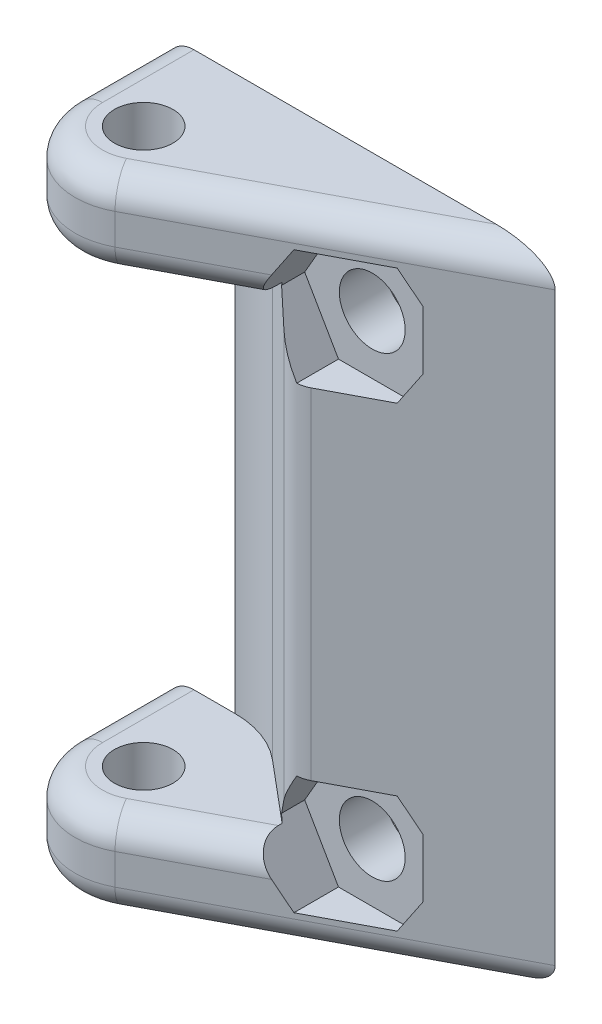
SolidWorks part; units mm, degrees
ref_plane "Front Plane" through (0, 0, 0) normal (0, 0, 1) x (1, 0, 0)
ref_plane "Top Plane" through (0, 0, 0) normal (0, 1, 0) x (1, 0, 0)
ref_plane "Right Plane" through (0, 0, 0) normal (1, 0, 0) x (0, 0, -1)
sketch "Sketch1" plane through (0, 0, 0) normal (0, 1, 0) x (1, 0, 0)
  line L2 (-4.7625, 6.35) -> (-4.7625, 0)
  line L3 (2.2238, -4.2114) -> (22.225, 6.35)
  line L4 (22.225, 6.35) -> (-4.7625, 6.35)
  circle A0 centre (0, 0) radius 2.032
  arc A1 (-4.7625, 0) -> (2.2238, -4.2114) centre (0, 0) ccw
  dimension "D1" = 4.064
  dimension "D2" = 22.225
  dimension "D4" = 4.7625
  dimension "D5" = 6.35
extrude "Boss-Extrude1" add sketch "Sketch1" along normal mid plane 44.45
sketch "Sketch6" plane through (0, 0, 0) normal (0, 1, 0) x (1, 0, 0)
  line L0 (0, 6.35) -> (-4.7625, 6.35)
  line L1 (-4.7625, 6.35) -> (-4.7625, 0) construction
  line L2 (-4.7625, 6.35) -> (-4.7625, 0)
  line L3 (4.0817, 4.8644) -> (10.0027, -0.1039)
  line L4 (2.2238, -4.2114) -> (22.225, 6.35) construction
  line L5 (10.0027, -0.1039) -> (2.2238, -4.2114)
  arc A0 (-4.7625, 0) -> (2.2238, -4.2114) centre (0, 0) ccw
  arc A2 (4.0817, 4.8644) -> (0, 6.35) centre (0, 0) ccw
  dimension "D1" = 6.35
  dimension "D2" = 140
extrude "Cut-Extrude4" cut sketch "Sketch6" against normal mid plane 32.5437
sketch "Sketch13" plane through (0, 0, -6.35) normal (0, 0, -1) x (-1, 0, 0)
  line L0 (-12.7, 15.875) -> (-12.7, -15.875) construction
  circle A0 centre (-12.7, 15.875) radius 2.286
  circle A1 centre (-12.7, -15.875) radius 2.286
  point P4 (-12.7, 0)
  dimension "D1" = 4.572
  dimension "D2" = 31.75
  dimension "D3" = 12.7
extrude "Cut-Extrude9" cut sketch "Sketch13" against normal through all
sketch "Sketch14" plane through (0, 0, -6.35) normal (0, 0, -1) x (-1, 0, 0)
  line L1 (-10.3536, 19.939) -> (-15.0464, 19.939)
  line L2 (-15.0464, 19.939) -> (-17.3927, 15.875)
  line L3 (-17.3927, 15.875) -> (-15.0464, 11.811)
  line L4 (-15.0464, 11.811) -> (-10.3536, 11.811)
  line L5 (-10.3536, 11.811) -> (-8.0073, 15.875)
  line L6 (-8.0073, 15.875) -> (-10.3536, 19.939)
  line L7 (-8.0073, -15.875) -> (-10.3536, -11.811)
  line L8 (-10.3536, -11.811) -> (-15.0464, -11.811)
  line L9 (-15.0464, -11.811) -> (-17.3927, -15.875)
  line L10 (-17.3927, -15.875) -> (-15.0464, -19.939)
  line L11 (-15.0464, -19.939) -> (-10.3536, -19.939)
  line L12 (-10.3536, -19.939) -> (-8.0073, -15.875)
  circle A0 centre (-12.7, 15.875) radius 4.064 construction
  circle A1 centre (-12.7, -15.875) radius 4.064 construction
  dimension "D1" = 8.128
  dimension "D2" = 8.128
extrude "Cut-Extrude10" cut sketch "Sketch14" against normal through all from offset 3.175 offset against normal yes
fillet "Fillet1" radius 1.905 13 edges at (-4.7625, -22.225, -3.175) (-2.4587, -22.225, 4.0787) (12.2244, 22.225, -1.0693) (-2.4587, 22.225, 4.0787) (12.2244, -22.225, -1.0693) (-4.7625, 22.225, -3.175) (-4.7625, -16.2719, -3.175) (5.2301, -16.2719, 2.624) (-4.7625, 16.2719, -3.175) (-2.4587, 16.2719, 4.0787) (-2.4587, -16.2719, 4.0787) (5.2301, 16.2719, 2.624) (10.0027, 0, 0.1039)
